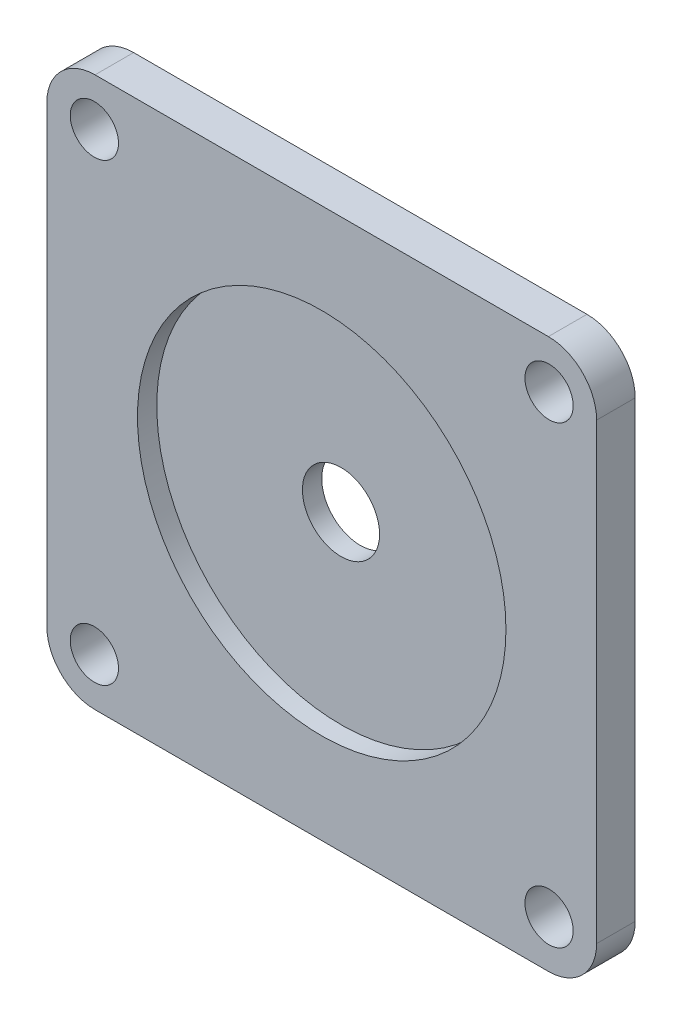
SolidWorks part; units mm, degrees
ref_plane "Ebene vorne" through (0, 0, 0) normal (0, 0, 1) x (1, 0, 0)
ref_plane "Ebene oben" through (0, 0, 0) normal (0, 1, 0) x (1, 0, 0)
ref_plane "Ebene rechts" through (0, 0, 0) normal (1, 0, 0) x (0, 0, -1)
sketch "Skizze1" plane through (0, 0, 0) normal (0, 0, 1) x (1, 0, 0)
  line L1 (-28.5, -28.5) -> (28.5, -28.5)
  line L2 (-28.5, -28.5) -> (-28.5, 28.5)
  line L3 (-28.5, 28.5) -> (28.5, 28.5)
  line L4 (28.5, -28.5) -> (28.5, 28.5)
  line L5 (-28.5, -28.5) -> (28.5, 28.5) construction
  line L6 (-28.5, 28.5) -> (28.5, -28.5) construction
  point P0 (0, 0)
  dimension "D1" = 57
  dimension "D2" = 57
extrude "Aufsatz-Linear austragen1" add sketch "Skizze1" along normal blind 4
hole_wizard "Ø5.0 (5) Durchmesser Bohrung2" positions "Skizze4" profile "Skizze5" hole size "Ø5.0" standard "ISO" end condition through all
sketch "Skizze4" plane through (0, 0, 4) normal (0, 0, 1) x (1, 0, 0)
  line L0 (-23.57, 23.57) -> (23.57, 23.57)
  line L1 (23.57, 23.57) -> (23.57, -23.57)
  line L2 (23.57, -23.57) -> (-23.57, -23.57)
  line L3 (-23.57, -23.57) -> (-23.57, 23.57)
  line L5 (0, 0) -> (0, 50000) construction
  line L6 (0, 0) -> (-50000, 0) construction
  point P1 (-23.57, 23.57)
  point P2 (23.57, 23.57)
  point P3 (23.57, -23.57)
  point P5 (-23.57, -23.57)
  dimension "D1" = 47.14
  dimension "D2" = 47.14
sketch "Skizze5" plane through (-23.57, 23.57, 4) normal (1, 0, 0) x (0, -1, 0)
  line L0 (0, 0) -> (0, 4)
  line L1 (0, 4) -> (2.5, 4)
  line L2 (2.5, 4) -> (2.5, 0)
  line L5 (2.5, 0) -> (0, 0)
  line L11 (0, -6.35) -> (0, 107.95) construction
  dimension "Bohrerdurchmesser" = 5
  dimension "Bohrungstiefe" = 4
fillet "Verrundung1" radius 5 4 edges at (-28.5, 28.5, 2) (-28.5, -28.5, 2) (28.5, -28.5, 2) (28.5, 28.5, 2)
sketch "Skizze6" plane through (0, 0, 4) normal (0, 0, 1) x (1, 0, 0)
  circle A0 centre (0, 0) radius 19.1
  dimension "D1" = 38.2
extrude "Schnitt-Linear austragen1" cut sketch "Skizze6" against normal blind 2
hole_wizard "Ø8.0 (8) Durchmesser Bohrung1" positions "Skizze7" profile "Skizze8" hole size "Ø8.0" standard "ISO" end condition through all
sketch "Skizze7" plane through (0, 0, 2) normal (0, 0, 1) x (1, 0, 0)
  point P0 (0, 0)
sketch "Skizze8" plane through (0, 0, 2) normal (1, 0, 0) x (0, -1, 0)
  line L0 (0, 0) -> (0, 2)
  line L1 (0, 2) -> (4, 2)
  line L2 (4, 2) -> (4, 0)
  line L5 (4, 0) -> (0, 0)
  line L11 (0, -6.35) -> (0, 107.95) construction
  dimension "Bohrerdurchmesser" = 8
  dimension "Bohrungstiefe" = 2
